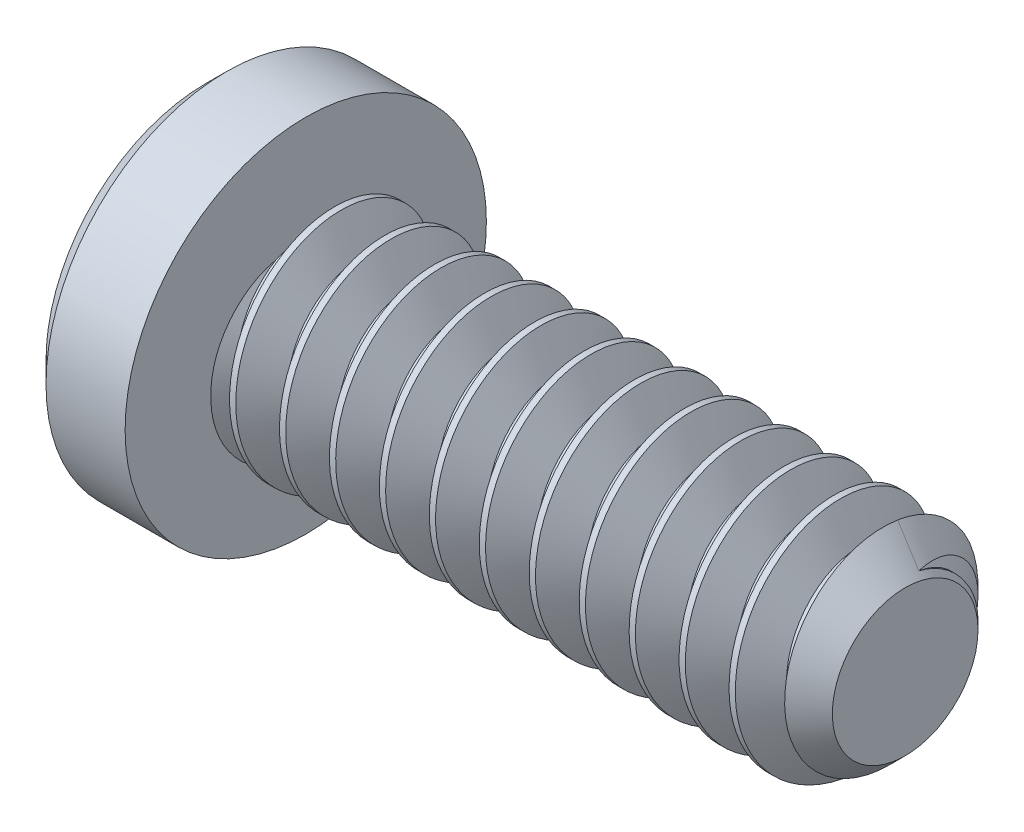
SolidWorks part; units mm, degrees
ref_plane "Front Plane" through (0, 0, 0) normal (0, 0, 1) x (1, 0, 0)
ref_plane "Top Plane" through (0, 0, 0) normal (0, 1, 0) x (1, 0, 0)
ref_plane "Right Plane" through (0, 0, 0) normal (1, 0, 0) x (0, 0, -1)
sketch "Sketch1" plane through (0, 0, 0) normal (0, 0, 1) x (1, 0, 0)
  line L0 (4.7625, 0) -> (-4.7625, 0) construction
  line L1 (4.7625, 1.7526) -> (4.7625, -1.7526) construction
  line L2 (-4.7625, 2.8702) -> (-4.7625, -2.8702) construction
  line L3 (-4.7625, 2.8702) -> (-6.0198, 2.8702) construction
  line L4 (-6.0198, 2.8702) -> (-6.35, 2.54) construction
  line L5 (-6.35, 2.54) -> (-6.35, -2.54) construction
  line L6 (-6.35, -2.54) -> (-6.0198, -2.8702) construction
  line L7 (-6.0198, -2.8702) -> (-4.7625, -2.8702) construction
  point P7 (-5.08, 0)
  point P12 (1.5875, -1.7526)
  dimension "D1" = 45
  dimension "Dec." = 3.5052
  dimension "Length" = 9.525
  dimension "Head Dia" = 5.7404
  dimension "Head Height" = 1.5875
  dimension "Hex Depth" = 1.27
  dimension "Chamfer" = 0.3302
  dimension "D2" = 3.175
ref_plane "Plane1" through (4.7625, 0, 0) normal (1, 0, 0) x (0, 0, -1)
ref_plane "Plane2" through (-6.35, 0, 0) normal (1, 0, 0) x (0, 0, -1)
sketch "Sketch2" plane through (4.7625, 0, 0) normal (1, 0, 0) x (0, 0, -1)
  circle A0 centre (0, 0) radius 1.7526
extrude "Boss-Extrude1" add sketch "Sketch2" against normal up to vertex (9.525 mm away) up to point (-4.7625, 0, 0)
sketch "Sketch3" plane through (4.7625, 0, 0) normal (1, 0, 0) x (0, 0, -1)
  circle A0 centre (0, 0) radius 1.7526 construction
  circle A1 centre (0, 0) radius 1.7526
curve "Helix/Spiral1" pitch 0.7937 height 10.3188 radius 1.7526 centre (4.7625, 0, 0) axis (-1, 0, 0) start towards (0, 1, 0) parameters "Pitch"=0.7937
chamfer "Chamfer1" distance 0.5953 angle 45 1 edges at (4.7625, 0, -1.7526)
sketch "Sketch5" plane through (0, 0, 0) normal (0, 0, 1) x (1, 0, 0)
  line L0 (4.4152, 1.7526) -> (5.1098, 1.7526)
  line L1 (5.1098, 1.7526) -> (4.8121, 1.237)
  line L2 (4.8121, 1.237) -> (4.7129, 1.237)
  line L3 (4.7129, 1.237) -> (4.4152, 1.7526)
  line L4 (4.7625, 1.237) -> (4.7625, 1.7526) construction
  line L5 (4.5641, 1.4948) -> (4.9609, 1.4948) construction
  dimension "D1" = 60
  dimension "D2" = 0.3969
  dimension "D3" = 0.0992
sweep "Cut-Sweep1" cut profiles "Sketch5" path "Helix/Spiral1" align with end faces yes
sketch "Sketch4" plane through (-6.35, 0, 0) normal (1, 0, 0) x (0, 0, -1)
  line L0 (-2.8702, 0.7937) -> (2.8702, 0.7937) construction
  line L1 (0, 0.9165) -> (-0.7937, 0.4583)
  line L2 (-0.7937, 0.4583) -> (-0.7937, -0.4583)
  line L3 (-0.7937, -0.4583) -> (0, -0.9165)
  line L4 (0, -0.9165) -> (0.7937, -0.4583)
  line L5 (0.7937, -0.4583) -> (0.7937, 0.4583)
  line L6 (0.7937, 0.4583) -> (0, 0.9165)
  line L7 (0, 0) -> (0, 0.7937) construction
  circle A0 centre (0, 0) radius 0.7937 construction
  dimension "Hex Size" = 1.5875
  dimension "D1" = 5.7404
  dimension "D2" = 0.7937
sketch "Sketch6" plane through (0, 0, 0) normal (0, 0, 1) x (1, 0, 0)
  line L0 (-6.0198, 2.8702) -> (-6.35, 2.54) construction
  line L1 (-4.7625, 2.8702) -> (-6.0198, 2.8702) construction
  line L2 (-4.7625, 2.8702) -> (-4.7625, -2.8702) construction
  line L3 (-6.35, 2.54) -> (-6.35, -2.54) construction
  line L4 (-6.0198, 2.8702) -> (-6.35, 2.54)
  line L5 (-4.7625, 2.8702) -> (-6.0198, 2.8702)
  line L6 (-4.7625, 2.8702) -> (-4.7625, 0)
  line L7 (-6.35, 2.54) -> (-6.35, 0)
  line L8 (-4.7625, 0) -> (-6.35, 0) construction
  line L9 (-4.7625, 0) -> (-6.35, 0)
revolve "Revolve1" add sketch "Sketch6" angle 360 about L8
extrude "Cut-Extrude1" cut sketch "Sketch4" along normal up to vertex (1.27 mm away) up to point (-5.08, 0, 0)
sketch "Sketch8" plane through (-6.35, 0, 0) normal (-1, 0, 0) x (0, 0, 1)
  circle A1 centre (0, 0) radius 0.9165
extrude "Cut-Extrude2" cut sketch "Sketch8" against normal through all draft 45
equation "\"D3@Helix/Spiral1\" = \"Length@Sketch1\"+\"Pitch@Helix/Spiral1\""
equation "\"D3@Sketch5\" = \"Pitch@Helix/Spiral1\"*.125"
equation "\"D2@Sketch5\" = \"Pitch@Helix/Spiral1\"*.50"
equation "\"D1@Chamfer1\" = \"Pitch@Helix/Spiral1\"*.75"
equation "\"D2@Sketch1\" = \"Pitch@Helix/Spiral1\"*4"
equation "\"D1@Sketch4\" = \"Head Dia@Sketch1\""
